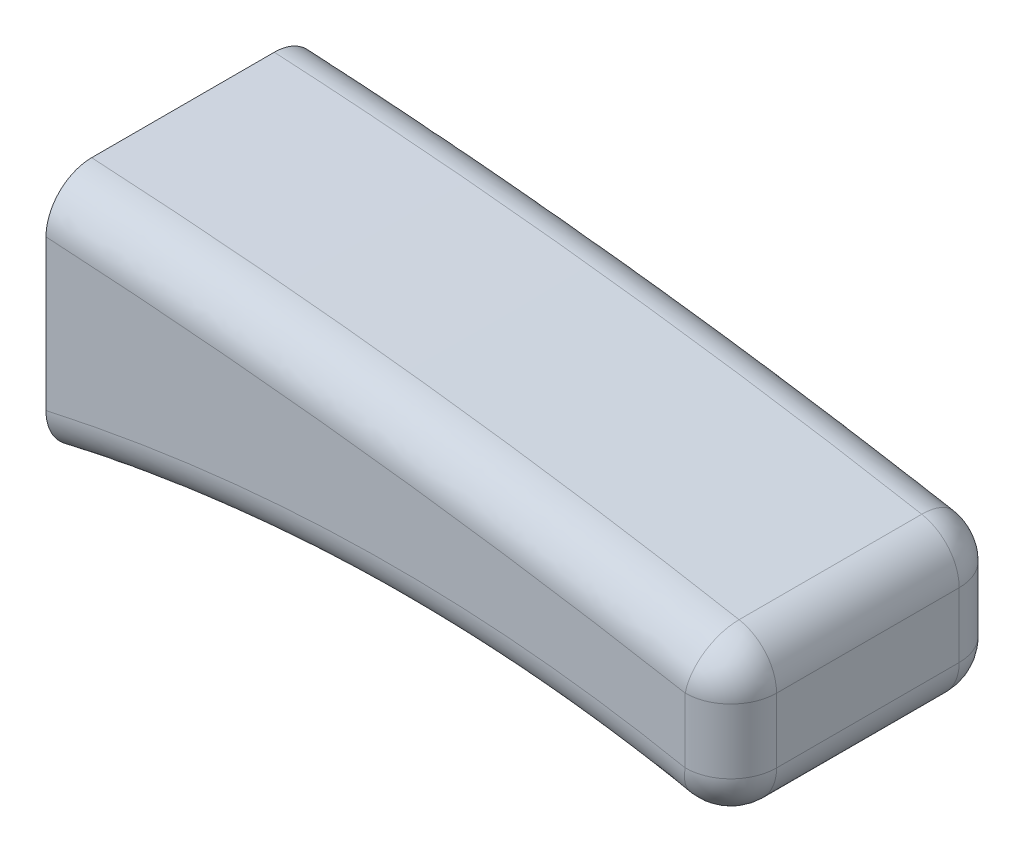
SolidWorks part; units mm, degrees
ref_plane "Front Plane" through (0, 0, 0) normal (0, 0, 1) x (1, 0, 0)
ref_plane "Top Plane" through (0, 0, 0) normal (0, 1, 0) x (1, 0, 0)
ref_plane "Right Plane" through (0, 0, 0) normal (1, 0, 0) x (0, 0, -1)
sketch "Sketch1" plane through (0, 0, 0) normal (1, 0, 0) x (0, 0, -1)
  line L1 (-30, -26.6) -> (30, -26.6)
  line L2 (-30, -26.6) -> (-30, 26.6)
  line L3 (-30, 26.6) -> (30, 26.6)
  line L4 (30, -26.6) -> (30, 26.6)
  line L5 (-30, -26.6) -> (30, 26.6) construction
  line L6 (-30, 26.6) -> (30, -26.6) construction
  point P0 (0, 0)
  dimension "D1" = 53.2
  dimension "D2" = 60
extrude "Boss-Extrude1" add sketch "Sketch1" along normal blind 150
sketch "Sketch2" plane through (0, 0, 0) normal (0, 0, 1) x (1, 0, 0)
  line L8 (0, 26.6) -> (150, 26.6)
  line L9 (0, 26.6) -> (0, -26.6) construction
  line L10 (0, -26.6) -> (150, -26.6)
  line L11 (150, 26.6) -> (150, 8.3434)
  spline S0 degree 2 poles (0, -26.6) (77.2627, -9.0382) (150, -26.6) knots 0 0 0 0.923796 0.923796 0.923796
  spline S1 degree 2 poles (0, 26.6) (75.9012, 22.423) (150, 8.3434) knots 0 0 0 0.565442 0.565442 0.565442
  dimension "D1" = 34.9434
  dimension "D2" = 18.2566
extrude "Cut-Extrude2" cut sketch "Sketch2" against normal blind 150 and the other way blind 150
fillet "Fillet3" radius 10 8 edges at (150, -26.6, 0) (150, -9.1283, 30) (150, -9.1283, -30) (150, 8.3434, 0)
